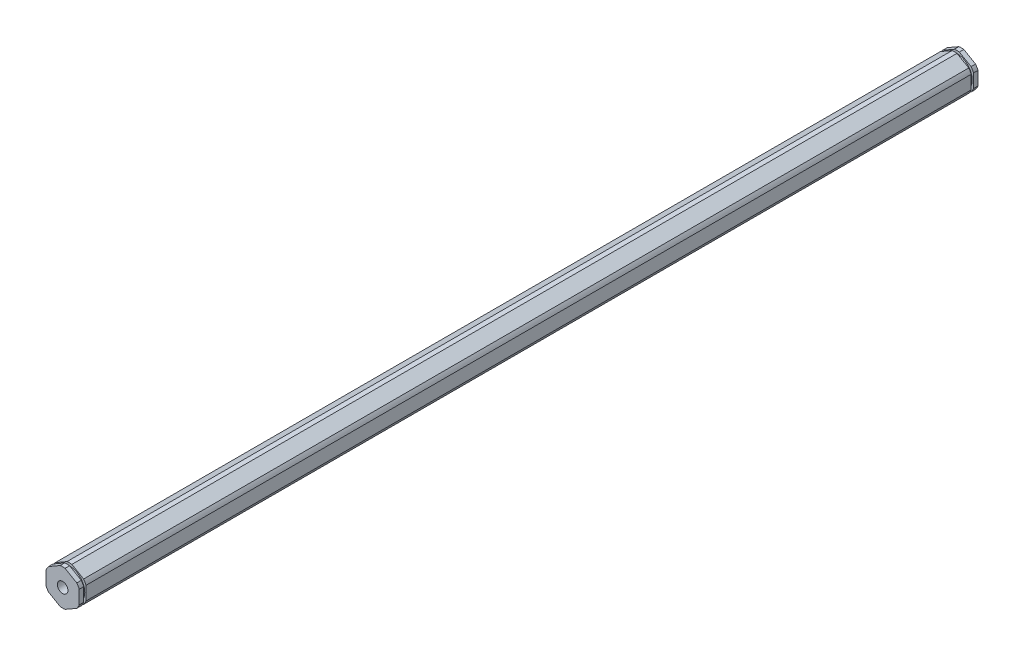
SolidWorks part; units mm, degrees
ref_plane "Front Plane" through (0, 0, 0) normal (0, 0, 1) x (1, 0, 0)
ref_plane "Top Plane" through (0, 0, 0) normal (0, 1, 0) x (1, 0, 0)
ref_plane "Right Plane" through (0, 0, 0) normal (1, 0, 0) x (0, 0, -1)
sketch "Sketch1" plane through (0, 0, 0) normal (0, 0, 1) x (1, 0, 0)
  line L1 (0, 7.3323) -> (-6.35, 3.6662)
  line L2 (-6.35, 3.6662) -> (-6.35, -3.6662)
  line L3 (-6.35, -3.6662) -> (0, -7.3323)
  line L4 (0, -7.3323) -> (6.35, -3.6662)
  line L5 (6.35, -3.6662) -> (6.35, 3.6662)
  line L6 (6.35, 3.6662) -> (0, 7.3323)
  circle A0 centre (0, 0) radius 6.35 construction
  circle A1 centre (0, 0) radius 6.858
  dimension "D1" = 12.7
  dimension "D2" = 13.716
extrude "Boss-Extrude1" add sketch "Sketch1" along normal mid plane 343.3445 contours L5 A1 L6 L1 L2 L3 L4 region at (0, 0, 0)
hole_wizard "#10-32 Tapped Hole1" positions "3DSketch1" profile "Sketch2" tap size "#10-32" standard "ANSI Inch"
sketch3d "3DSketch1"
  line L0 (0, 0, 171.6722) -> (0, 0, -171.6722) construction
  line L1 (0, 0, 171.6722) -> (0, 0, -171.6722) construction
  point P0 (0, 0, 171.6722)
  point P4 (0, 0, -171.6722)
sketch "Sketch2" plane through (0, 0, 171.6722) normal (1, 0, 0) x (0, -1, 0)
  line L0 (0, 0) -> (0, 17.5608)
  line L1 (0, 17.5608) -> (2.0193, 16.3474)
  line L2 (2.0193, 16.3474) -> (2.0193, 0)
  line L5 (2.0193, 0) -> (0, 0)
  line L10 (0, 17.5608) -> (-2.0193, 16.3474) construction
  line L11 (0, -6.35) -> (0, 107.95) construction
  dimension "Tap Drill Dia." = 4.0386
  dimension "Tap Drill Depth" = 16.3474
  dimension "Drill Angle" = 118
cosmetic thread "Hole Thread1" parameters "D1"=13.97, "D2"=4.826
cosmetic thread "Hole Thread2" parameters "D1"=13.97, "D2"=4.826
sketch "Sketch5" plane through (0, 0, 0) normal (1, 0, 0) x (0, 0, -1)
  line L0 (171.6722, 6.858) -> (-171.6722, 6.858) construction
  line L1 (-169.9577, 6.858) -> (-169.0687, 6.858)
  line L2 (-169.9577, 6.858) -> (-169.9577, 5.8547)
  line L3 (-169.9577, 5.8547) -> (-169.0687, 5.8547)
  line L4 (-169.0687, 6.858) -> (-169.0687, 5.8547)
  line L5 (-165.0472, 0) -> (-158.8423, 0) construction
  dimension "D1" = 5.8547
  dimension "D2" = 0.889
  dimension "D3" = 1.7145
revolve "Cut-Revolve1" cut sketch "Sketch5" angle 360 about L5
mirror "Mirror1" about plane through (0, 0, 0) normal (0, 0, 1) of "Cut-Revolve1"
